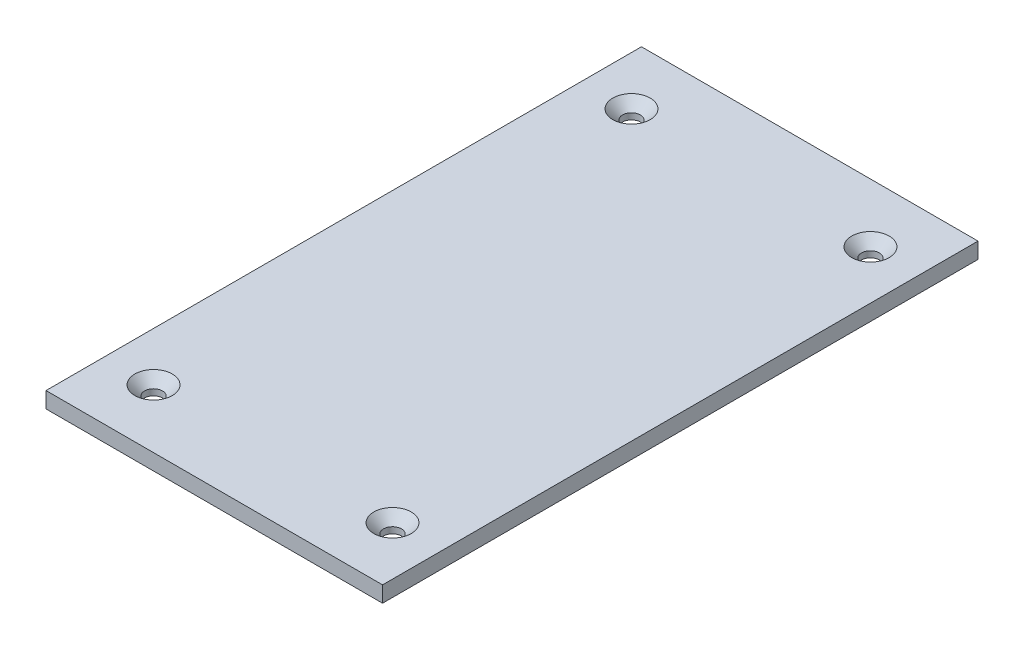
SolidWorks part; units mm, degrees
material "1060 Alloy"
ref_plane "Front Plane" through (0, 0, 0) normal (0, 0, 1) x (1, 0, 0)
ref_plane "Top Plane" through (0, 0, 0) normal (0, 1, 0) x (1, 0, 0)
ref_plane "Right Plane" through (0, 0, 0) normal (1, 0, 0) x (0, 0, -1)
sketch "Sketch1" plane through (0, 0, 0) normal (0, 1, 0) x (1, 0, 0)
  line L0 (42.25, -74.75) -> (-42.25, 74.75) construction
  line L1 (-42.25, 74.75) -> (42.25, 74.75)
  line L2 (-42.25, 74.75) -> (-42.25, -74.75)
  line L3 (-42.25, -74.75) -> (42.25, -74.75)
  line L4 (42.25, 74.75) -> (42.25, -74.75)
  dimension "D1" = 84.5
  dimension "D2" = 149.5
sheet metal parameters "Sheet-Metal1" thickness 4 parameters "D1"=5
base flange "Base-Flange1" sketch "Sketch1" thickness 4 reverse thickness direction no parameters "D1"=5
sketch "Sketch4" plane through (0, 0, 0) normal (0, 1, 0) x (1, 0, 0)
  line L0 (-30, -60) -> (30, 60) construction
  line L1 (30, 60) -> (-30, 60) construction
  line L2 (30, 60) -> (30, -60) construction
  line L3 (30, -60) -> (-30, -60) construction
  line L4 (-30, 60) -> (-30, -60) construction
  line L5 (30, 60) -> (29.4706, 59.7353) construction
  dimension "D1" = 60
  dimension "D2" = 120
hole_wizard "CSK for M4 Flat Head Machine Screw1" positions "Sketch6" profile "Sketch5" countersink size "M4" standard "ANSI Metric" end condition through all
sketch "Sketch6" plane through (0, 0, 0) normal (0, 1, 0) x (1, 0, 0)
  point P0 (30, 60)
  point P3 (-30, 60)
  point P6 (-30, -60)
  point P9 (30, -60)
sketch "Sketch5" plane through (30, 0, -60) normal (1, 0, 0) x (0, 0, 1)
  line L0 (0, 0) -> (0, 4)
  line L1 (0, 4) -> (2.25, 4)
  line L2 (2.25, 4) -> (2.25, 2.45)
  line L3 (2.25, 2.45) -> (4.7, 0)
  line L5 (4.7, 0) -> (0, 0)
  line L6 (-2.25, 2.45) -> (-4.7, 0) construction
  line L11 (0, -6.35) -> (0, 107.95) construction
  dimension "Thru Hole Dia." = 4.5
  dimension "Thru Hole Depth" = 4
  dimension "Near C'Sink Dia." = 9.4
  dimension "Near C'Sink Angle" = 90
flat pattern "Flat-Pattern1" [suppressed]
sketch "Bend-Lines1" plane through (0, 0, 0) normal (0, 1, 0) x (1, 0, 0)
sketch3d "Bounding-Box1" [suppressed]
  line L0 (-42.25, 74.75, 0) -> (-42.25, -74.75, 0) construction
  line L1 (42.25, 74.75, 0) -> (42.25, -74.75, 0) construction
  line L2 (-42.25, 74.75, 0) -> (42.25, 74.75, 0) construction
  line L3 (-42.25, -74.75, 0) -> (42.25, -74.75, 0) construction
